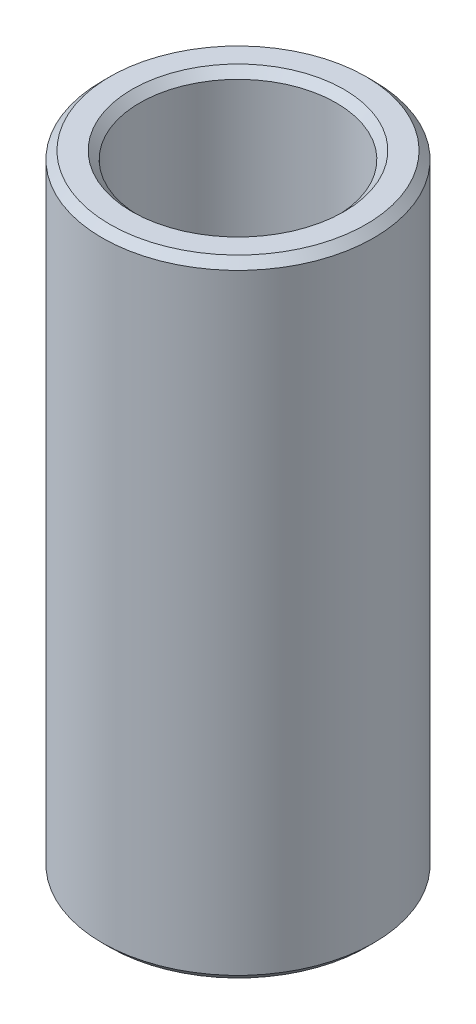
SolidWorks part; units mm, degrees
ref_plane "Front Plane" through (0, 0, 0) normal (0, 0, 1) x (1, 0, 0)
ref_plane "Top Plane" through (0, 0, 0) normal (0, 1, 0) x (1, 0, 0)
ref_plane "Right Plane" through (0, 0, 0) normal (1, 0, 0) x (0, 0, -1)
sketch "Sketch1" plane through (0, 0, 0) normal (0, 1, 0) x (1, 0, 0)
  circle A0 centre (0, 0) radius 22.5
  dimension "SLEEVE_OD" = 45
extrude "Boss-Extrude1" add sketch "Sketch1" along normal blind 103.7169
sketch "Sketch2" plane through (0, 0, 0) normal (0, 1, 0) x (1, 0, 0)
  circle A0 centre (0, 0) radius 16.268
  dimension "BORE_D" = 32.5361
extrude "Cut-Extrude1" cut sketch "Sketch2" along normal through all
chamfer "Chamfer1" distance 1.2888 angle 45 4 edges at (0, 103.7169, 16.268) (0, 0, 16.268) (0, 0, 22.5) (0, 103.7169, 22.5)
